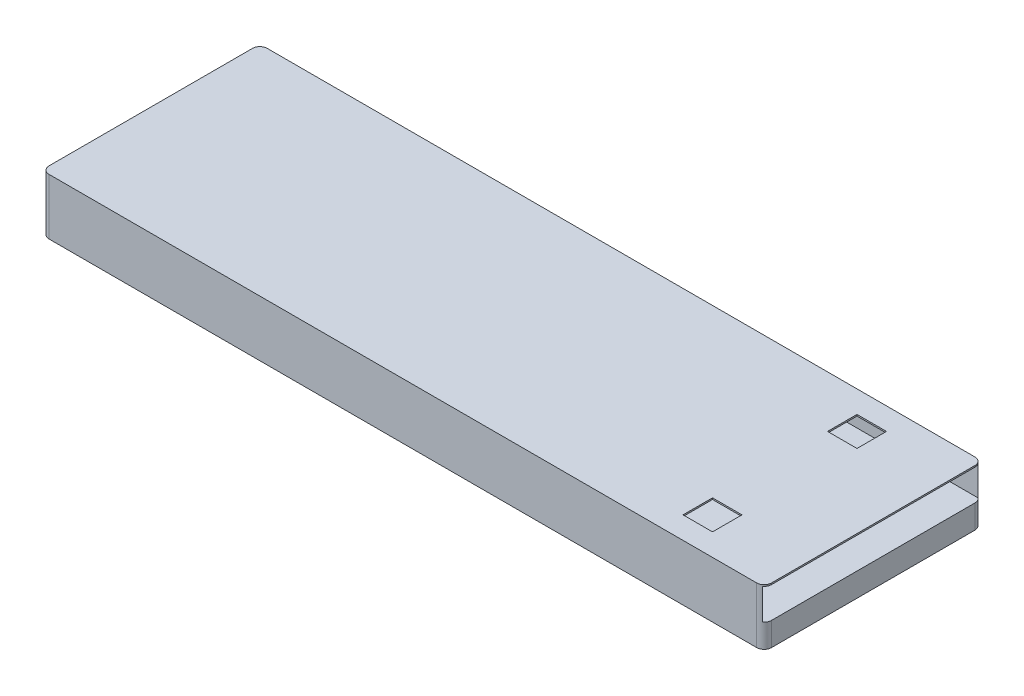
SolidWorks part; units mm, degrees
ref_plane "Front Plane" through (0, 0, 0) normal (0, 0, 1) x (1, 0, 0)
ref_plane "Top Plane" through (0, 0, 0) normal (0, 1, 0) x (1, 0, 0)
ref_plane "Right Plane" through (0, 0, 0) normal (1, 0, 0) x (0, 0, -1)
sketch "Sketch1" plane through (0, 0, 0) normal (0, 1, 0) x (1, 0, 0)
  line L1 (0, 0) -> (-49, 0)
  line L2 (0, 0) -> (0, 14.8)
  line L3 (0, 14.8) -> (-49, 14.8)
  line L4 (-49, 0) -> (-49, 14.8)
  dimension "D1" = 49
  dimension "D2" = 14.8
extrude "Boss-Extrude1" add sketch "Sketch1" against normal blind 3.8
sketch "Sketch2" plane through (0, 0, 0) normal (1, 0, 0) x (0, 0, -1)
  line L3 (14.7, -0.1) -> (0.1, -0.1)
  line L6 (0, 0) -> (14.8, 0) construction
  line L7 (0.1, -0.1) -> (0.1, -3.7)
  line L8 (0.1, -3.7) -> (14.7, -3.7)
  line L9 (14.7, -3.7) -> (14.7, -0.1)
  line L10 (0, -3.8) -> (0, 0) construction
  line L11 (14.8, -3.8) -> (14.8, 0) construction
  line L12 (0, -3.8) -> (14.8, -3.8) construction
  point P6 (0, -1.9)
  dimension "D1" = 0.1
  dimension "D2" = 0.1
  dimension "D3" = 0.1
  dimension "D4" = 0.1
extrude "Cut-Extrude1" cut sketch "Sketch2" against normal blind 48
ref_plane "Plane1" through (0, 0, 0) normal (1, 0, 0) x (0, 0, -1)
sketch "Sketch3" plane through (0, 0, 0) normal (1, 0, 0) x (0, 0, -1)
  line L0 (14.7, -3.7) -> (14.7, -0.1) construction
  line L1 (0.1, -3.7) -> (14.7, -3.7)
  line L2 (0.1, -3.7) -> (0.1, -2.2)
  line L3 (0.1, -2.2) -> (14.7, -2.2)
  line L4 (14.7, -3.7) -> (14.7, -2.2)
  dimension "D1" = 1.5
extrude "Boss-Extrude2" add sketch "Sketch3" against normal up to surface (48 mm away) up to face at (-48, -1.9, -7.4)
sketch "Sketch5" plane through (0, 0, 0) normal (0, 1, 0) x (1, 0, 0)
  line L0 (0, 0) -> (0, 14.8) construction
  line L1 (-5, 13.3) -> (-7, 13.3)
  line L2 (-5, 13.3) -> (-5, 11.3)
  line L3 (-5, 11.3) -> (-7, 11.3)
  line L4 (-7, 13.3) -> (-7, 11.3)
  line L5 (-5, 3.5) -> (-7, 3.5)
  line L6 (-5, 3.5) -> (-5, 1.5)
  line L7 (-5, 1.5) -> (-7, 1.5)
  line L8 (-7, 3.5) -> (-7, 1.5)
  line L9 (-49, 0) -> (0, 0) construction
  line L10 (0, 14.8) -> (-49, 14.8) construction
  dimension "D1" = 5
  dimension "D2" = 5
  dimension "D3" = 1.5
  dimension "D4" = 1.5
  dimension "D5" = 2
  dimension "D6" = 2
  dimension "D7" = 2
  dimension "D8" = 2
extrude "Cut-Extrude2" cut sketch "Sketch5" against normal up to surface (2.2 mm away) up to face at (-24, -2.2, -7.4)
fillet "Fillet1" radius 0.5 4 edges at (0, -1.9, 0) (0, -1.9, -14.8) (-49, -1.9, -14.8) (-49, -1.9, 0)
sketch "Sketch6" plane through (0, -3.8, 0) normal (0, -1, 0) x (1, 0, 0)
  line L0 (-49, -14.3) -> (-49, -0.5) construction
  line L6 (-34, -3.9) -> (-25, -3.9)
  line L7 (-34, -3.9) -> (-34, -10.9)
  line L8 (-34, -10.9) -> (-25, -10.9)
  line L10 (-48.5, -14.8) -> (-0.5, -14.8) construction
  line L11 (-25, -3.9) -> (-25, -10.9)
  line L12 (-48.5, 0) -> (-0.5, 0) construction
  line L13 (-21.0095, 0) -> (-21.0095, -14.8) construction
  point P14 (-34, -7.4)
  point P15 (-25, -7.4)
  point P16 (-21.0095, -7.4)
  dimension "D1" = 15
  dimension "D2" = 9
  dimension "D3" = 7
extrude "Boss-Extrude3" add sketch "Sketch6" along normal blind 1.7
fillet "Fillet2" radius 1 4 edges at (-29.5, -5.5, -10.9) (-25, -5.5, -7.4) (-29.5, -5.5, -3.9) (-34, -5.5, -7.4)
